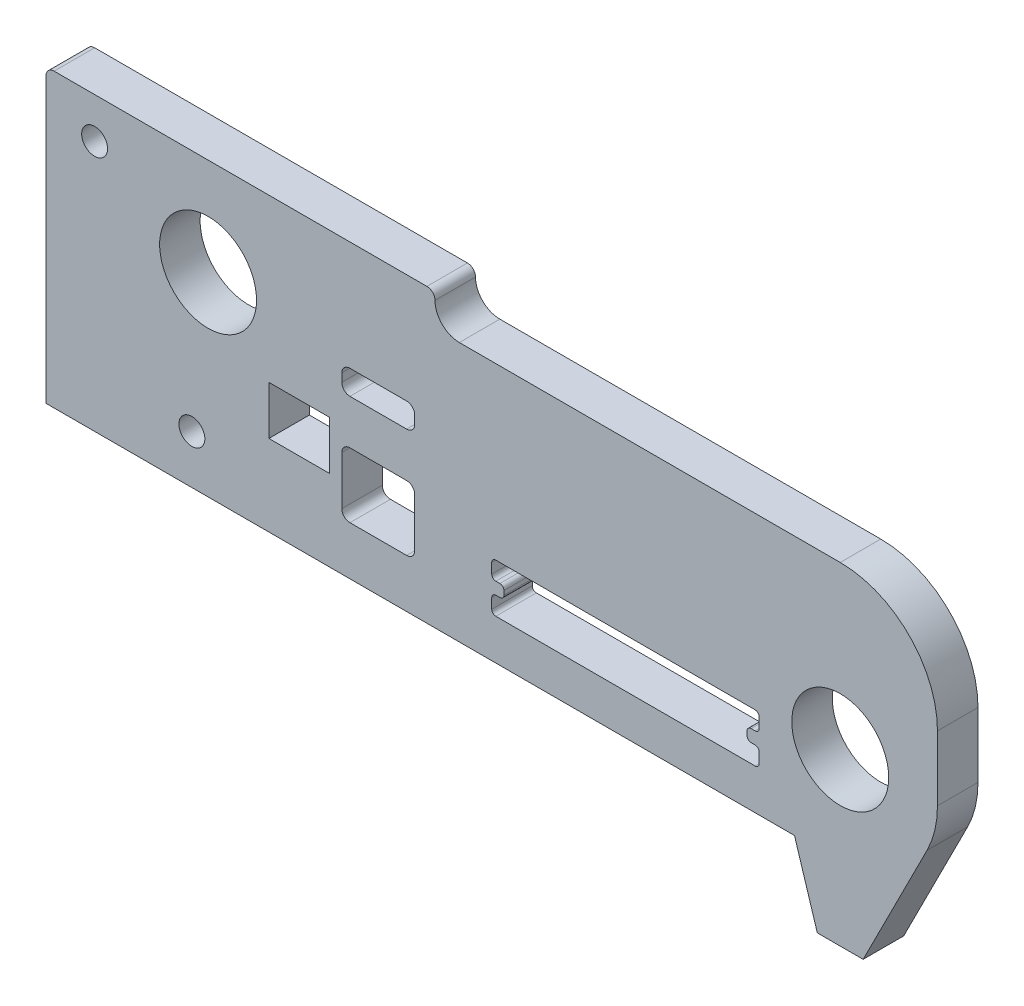
SolidWorks part; units mm, degrees
material "6061-T6 Black anodised"
ref_plane "Front Plane" through (0, 0, 0) normal (0, 0, 1) x (1, 0, 0)
ref_plane "Top Plane" through (0, 0, 0) normal (0, 1, 0) x (1, 0, 0)
ref_plane "Right Plane" through (0, 0, 0) normal (1, 0, 0) x (0, 0, -1)
sketch "Sketch1" plane through (0, 0, 0) normal (0, 0, 1) x (1, 0, 0)
  line L0 (72.3566, -24) -> (75.1721, -33)
  line L1 (-20, 12) -> (28, 12)
  line L2 (-20, 12) -> (-20, -24)
  line L3 (-20, -24) -> (72.3566, -24)
  line L4 (90, -4) -> (90, -12)
  line L5 (75.1721, -33) -> (80.8279, -33)
  line L6 (88.7087, -17.4151) -> (80.8279, -33)
  line L7 (25.5, -4.5) -> (25.5, -10) construction
  line L8 (16.5, -10) -> (25.5, -10)
  line L9 (16.5, -10) -> (16.5, -18)
  line L10 (16.5, -18) -> (25.5, -18)
  line L11 (25.5, -10) -> (25.5, -18)
  line L12 (16.5, -1.5) -> (25.5, -1.5)
  line L13 (16.5, -1.5) -> (16.5, -4.5)
  line L14 (16.5, -4.5) -> (25.5, -4.5)
  line L15 (25.5, -1.5) -> (25.5, -4.5)
  line L16 (28, 12) -> (28, 8)
  line L17 (7.5, -8) -> (15, -8)
  line L18 (7.5, -8) -> (7.5, -14)
  line L19 (7.5, -14) -> (15, -14)
  line L20 (15, -8) -> (15, -14)
  line L21 (28, 8) -> (78, 8)
  circle A0 centre (0, 0) radius 5.98
  circle A1 centre (78, -12) radius 5.98
  arc A3 (88.7087, -17.4151) -> (90, -12) centre (78, -12) ccw
  circle A4 centre (-14, 7) radius 1.6
  circle A5 centre (-2, -18) radius 1.6
  arc A6 (90, -4) -> (78, 8) centre (78, -4) ccw
  point P4 (-20, -6)
  point P13 (78, -33)
  point P29 (25.5, -10)
  dimension "D3" = 11.96
  dimension "D4" = 98
  dimension "D8" = 3.2
  dimension "D10" = 13
  dimension "D11" = 10
  dimension "D12" = 12
  dimension "D23" = 12
  dimension "D1" = 9
  dimension "D5" = 20
  dimension "D6" = 36
  dimension "D7" = 4
  dimension "D9" = 14
  dimension "D13" = 5.5
  dimension "D14" = 8
  dimension "D15" = 3
  dimension "D16" = 9
  dimension "D17" = 16.5
  dimension "D18" = 10
  dimension "D19" = 9
  dimension "D20" = 7.5
  dimension "D21" = 8
  dimension "D22" = 6
  dimension "D24" = 48
  dimension "D25" = 12
  dimension "D26" = 24
  dimension "D27" = 2
extrude "Boss-Extrude1" add sketch "Sketch1" along normal blind 5
fillet "Fillet1" radius 1 8 edges at (16.5, -4.5, 2.5) (16.5, -1.5, 2.5) (25.5, -1.5, 2.5) (25.5, -4.5, 2.5) (25.5, -18, 2.5) (25.5, -10, 2.5) (16.5, -10, 2.5) (16.5, -18, 2.5)
fillet "Fillet2" radius 3 1 edges at (28, 8, 2.5)
fillet "Fillet3" radius 1 2 edges at (28, 12, 2.5) (-20, 12, 2.5)
sketch "Sketch2" plane through (0, 0, 5) normal (0, 0, 1) x (1, 0, 0)
  line L0 (35, -13) -> (68, -19) construction
  line L1 (35, -13) -> (68, -13)
  line L2 (35, -13) -> (35, -15.25)
  line L3 (35, -19) -> (68, -19)
  line L4 (68, -13) -> (68, -15.25)
  line L5 (36.5, -15.25) -> (35, -15.25)
  line L6 (36.5, -15.25) -> (36.5, -16.75)
  line L7 (36.5, -16.75) -> (35, -16.75)
  line L8 (68, -16.75) -> (68, -19)
  line L9 (36.5, -15.25) -> (35, -16.75) construction
  line L10 (36.5, -16.75) -> (35, -15.25) construction
  line L11 (66.5, -15.25) -> (68, -15.25)
  line L12 (66.5, -15.25) -> (66.5, -16.75)
  line L13 (66.5, -16.75) -> (68, -16.75)
  line L14 (-20, -24) -> (72.3566, -24) construction
  line L15 (66.5, -15.25) -> (68, -16.75) construction
  line L16 (66.5, -16.75) -> (68, -15.25) construction
  line L17 (68, -13) -> (35, -19) construction
  line L18 (35, -16.75) -> (35, -19)
  point P4 (35.75, -16)
  point P9 (67.25, -16)
  point P14 (51.5, -16)
  dimension "D1" = 1.5
  dimension "D2" = 33
  dimension "D3" = 6
  dimension "D4" = 1.5
  dimension "D5" = 68
  dimension "D6" = 5
extrude "Cut-Extrude1" cut sketch "Sketch2" against normal through all
fillet "Fillet4" radius 0.5 12 edges at (68, -13, 2.5) (68, -15.25, 2.5) (66.5, -15.25, 2.5) (66.5, -16.75, 2.5) (68, -16.75, 2.5) (68, -19, 2.5) (35, -19, 2.5) (35, -16.75, 2.5) (35, -13, 2.5) (35, -15.25, 2.5) (36.5, -16.75, 2.5) (36.5, -15.25, 2.5)
equation "\"y-cross-rib-thickness\"=6"
equation "\"y-rib-thickness\"=6"
equation "\"bed-plate-thickness\"=6"
equation "\"x-plate-thickness\"=5"
equation "\"rod-diameter\"=12"
equation "\"t-nut-hole-diameter\"=3"
equation "\"y-plate-thickness\"=5"
equation "\"D1@Boss-Extrude1\"=\"y-plate-thickness\""
